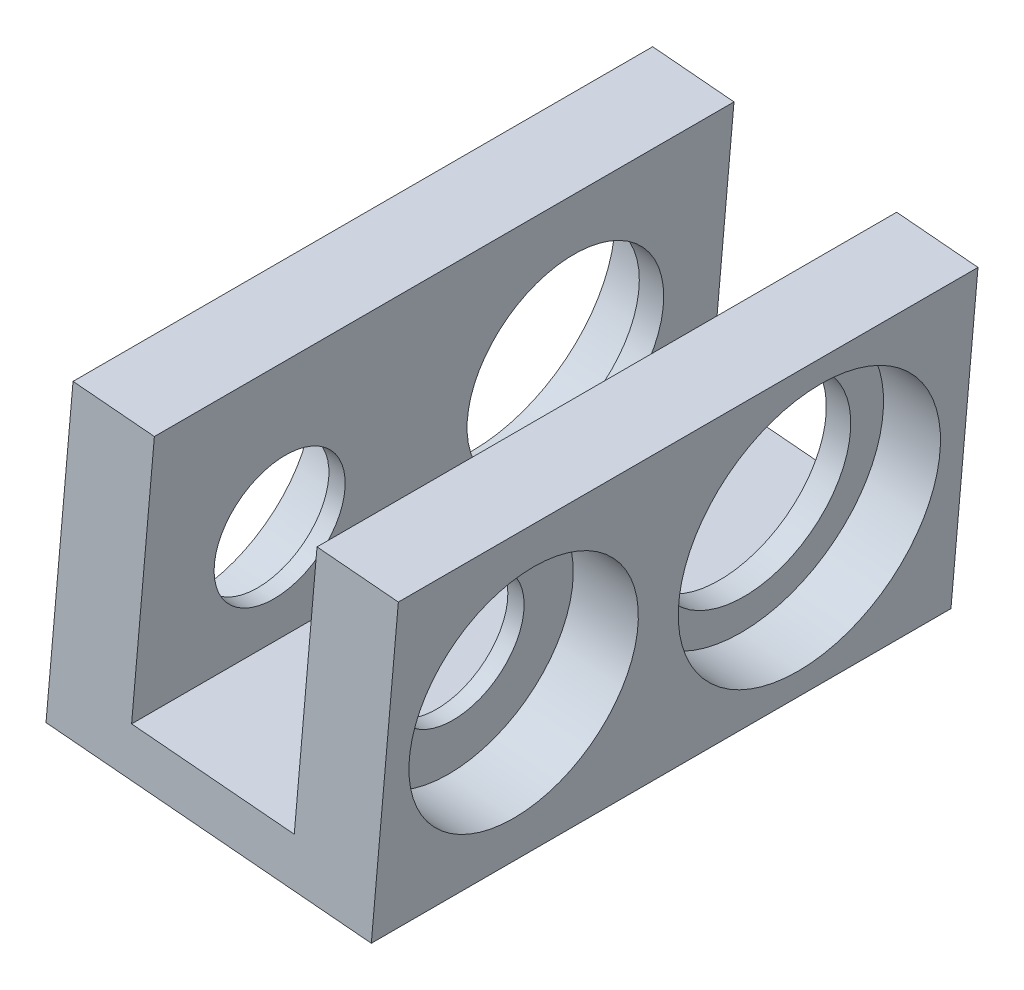
SolidWorks part; units mm, degrees
ref_plane "Front Plane" through (0, 0, 0) normal (0, 0, 1) x (1, 0, 0)
ref_plane "Top Plane" through (0, 0, 0) normal (0, 1, 0) x (1, 0, 0)
ref_plane "Right Plane" through (0, 0, 0) normal (1, 0, 0) x (0, 0, -1)
ref_axis "Axis1" through (0, 0, -88.99) along (0, 0, 1)
ref_plane "Plane1" through (0, 0, 0) normal (-0.9962, 0.0872, 0) x (0, 0, 1)
sketch "Sketch1" plane through (0, 0, 0) normal (-0.9962, 0.0872, 0) x (0, 0, 1)
  line L0 (0, 0) -> (0, 97.3301) construction
  line L9 (-88.99, 0) -> (88.99, 0) construction
  line L18 (-36.5, 38) -> (34.5, 38)
  line L19 (-36.5, 38) -> (-36.5, 0)
  line L20 (-36.5, 0) -> (34.5, 0)
  line L21 (34.5, 38) -> (34.5, 0)
  line L22 (-33.5, 19) -> (-33.5, 62.6427) construction
  line L23 (-17.5, 35) -> (44.9097, 35) construction
  line L24 (31.5, 19) -> (31.5, 63.5996) construction
  line L25 (-17.5, 3) -> (47.3057, 3) construction
  circle A0 centre (-17.5, 19) radius 12
  circle A1 centre (17.5, 19) radius 8
  circle A4 centre (-17.5, 19) radius 16 construction
  circle A5 centre (17.5, 19) radius 14 construction
  dimension "D1" = 16
  dimension "D2" = 24
  dimension "D6" = 3
  dimension "D5" = 28
  dimension "D4" = 32
  dimension "D3" = 35
  dimension "D7" = 3
  dimension "D8" = 3
  dimension "D9" = 3
extrude "Boss-Extrude1" add sketch "Sketch1" against normal blind 40
ref_plane "Plane2" through (0, 0, 0) normal (-0.0872, -0.9962, 0) x (0, 0, 1)
sketch "Sketch7" plane through (0, 0, 0) normal (-0.9962, 0.0872, 0) x (0, 0, 1)
  circle A0 centre (-17.5, 19) radius 16
  circle A1 centre (-17.5, 19) radius 12 construction
  dimension "D1" = 32
extrude "Cut-Extrude4" cut sketch "Sketch7" against normal blind 7
sketch "Sketch8" plane through (0, 0, 0) normal (-0.9962, 0.0872, 0) x (0, 0, 1)
  circle A0 centre (17.5, 19) radius 14
  circle A1 centre (17.5, 19) radius 8 construction
  dimension "D1" = 28
extrude "Cut-Extrude5" cut sketch "Sketch8" against normal blind 8
sketch "Sketch9" plane through (39.8478, -3.4862, 0) normal (0.9962, -0.0872, 0) x (0, 0, -1)
  circle A0 centre (17.5, 19) radius 16
  circle A1 centre (17.5, 19) radius 12 construction
  dimension "D1" = 32
extrude "Cut-Extrude6" cut sketch "Sketch9" against normal blind 7
sketch "Sketch10" plane through (39.8478, -3.4862, 0) normal (0.9962, -0.0872, 0) x (0, 0, -1)
  circle A0 centre (-17.5, 19) radius 14
  circle A1 centre (-17.5, 19) radius 8 construction
  dimension "D1" = 28
extrude "Cut-Extrude7" cut sketch "Sketch10" against normal blind 8
sketch "Sketch11" plane through (0, 0, 34.5) normal (0, 0, 1) x (1, 0, 0)
  line L0 (13.2739, 36.9838) -> (33.1978, 35.2407)
  line L1 (43.1597, 34.3692) -> (3.3119, 37.8554) construction
  line L2 (33.1978, 35.2407) -> (30.4088, 3.3625)
  line L4 (30.4088, 3.3625) -> (10.4849, 5.1056)
  line L5 (10.4849, 5.1056) -> (13.2739, 36.9838)
  line L6 (39.8478, -3.4862) -> (43.1597, 34.3692) construction
  line L7 (8.5316, 97.5165) -> (-8.5316, -97.5165) construction
  line L8 (-37.841, 3.3107) -> (37.841, -3.3107) construction
  dimension "D1" = 10
  dimension "D2" = 10
  dimension "D3" = 6
extrude "Cut-Extrude8" cut sketch "Sketch11" against normal through all
